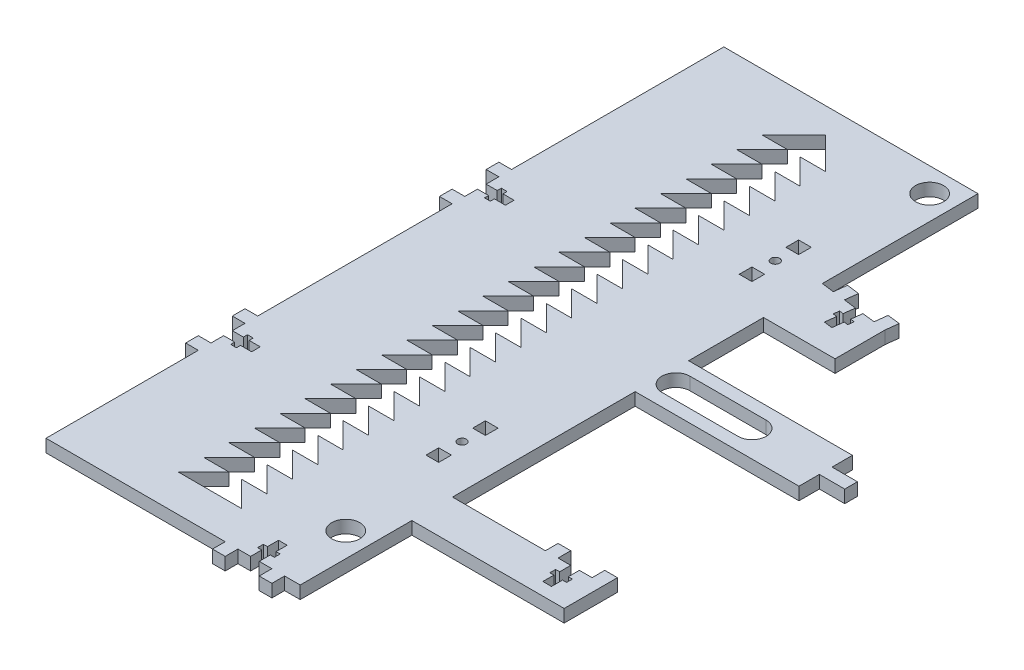
SolidWorks part; units mm, degrees
ref_plane "Front Plane" through (0, 0, 0) normal (0, 0, 1) x (1, 0, 0)
ref_plane "Top Plane" through (0, 0, 0) normal (0, 1, 0) x (1, 0, 0)
ref_plane "Right Plane" through (0, 0, 0) normal (1, 0, 0) x (0, 0, -1)
sketch "Axle Support Plate" plane through (0, 0, 0) normal (0, 1, 0) x (1, 0, 0)
  line L0 (51.4759, 157.4574) -> (51.4759, -134.6426) construction
  line L1 (38.7759, 169.5676) -> (38.7759, -103.4054) construction
  line L2 (0, 156.8676) -> (-15.875, 140.9926)
  line L3 (-15.875, 140.9926) -> (-3.175, 140.9926)
  line L4 (63.5861, -169.5676) -> (63.5861, -113.6876)
  line L5 (-63.5861, 169.5676) -> (63.5861, -169.5676) construction
  line L6 (-63.5861, -169.5676) -> (63.5861, 169.5676) construction
  line L7 (-63.5861, -63.6496) -> (-63.5861, 33.6324)
  line L8 (-63.5861, 169.5676) -> (63.5861, 169.5676)
  line L9 (0, 169.5676) -> (0, -169.5676) construction
  line L10 (15.875, 140.9926) -> (0, 156.8676)
  line L11 (-3.175, 140.9926) -> (-15.875, 128.2926)
  line L12 (-15.875, 128.2926) -> (-3.175, 128.2926)
  line L13 (15.875, 128.2926) -> (3.175, 140.9926)
  line L14 (-3.175, 128.2926) -> (-15.875, 115.5926)
  line L15 (-15.875, 115.5926) -> (-3.175, 115.5926)
  line L16 (15.875, 115.5926) -> (3.175, 128.2926)
  line L17 (63.5861, 11.4074) -> (4.2777, 11.4074) construction
  line L18 (-3.175, 115.5926) -> (-15.875, 102.8926)
  line L19 (-15.875, 102.8926) -> (-3.175, 102.8926)
  line L20 (15.875, 102.8926) -> (3.175, 115.5926)
  line L21 (-3.175, 102.8926) -> (-15.875, 90.1926)
  line L22 (-15.875, 90.1926) -> (-3.175, 90.1926)
  line L23 (55.7939, -169.5676) -> (63.5861, -169.5676)
  line L24 (15.875, 90.1926) -> (3.175, 102.8926)
  line L25 (-3.175, 90.1926) -> (-15.875, 77.4926)
  line L26 (-15.875, 77.4926) -> (-3.175, 77.4926)
  line L27 (15.875, 77.4926) -> (3.175, 90.1926)
  line L28 (-3.175, 77.4926) -> (-15.875, 64.7926)
  line L29 (-15.875, 64.7926) -> (-3.175, 64.7926)
  line L30 (15.875, 64.7926) -> (3.175, 77.4926)
  line L31 (-3.175, 64.7926) -> (-15.875, 52.0926)
  line L32 (-15.875, 52.0926) -> (-3.175, 52.0926)
  line L33 (15.875, 52.0926) -> (3.175, 64.7926)
  line L34 (-3.175, 52.0926) -> (-15.875, 39.3926)
  line L35 (-15.875, 39.3926) -> (-3.175, 39.3926)
  line L36 (15.875, 39.3926) -> (3.175, 52.0926)
  line L37 (63.5861, 24.7876) -> (145.5462, 24.7876)
  line L38 (145.5462, 24.7876) -> (145.5462, 14.5824)
  line L39 (145.5462, -1.9727) -> (63.5861, -1.9727)
  line L40 (70.6162, 11.4074) -> (108.7162, 11.4074) construction
  line L41 (70.6162, 18.4376) -> (108.7162, 18.4376)
  line L42 (70.6162, 4.3773) -> (108.7162, 4.3773)
  line L43 (145.5462, 8.2324) -> (158.2462, 8.2324)
  line L44 (158.2462, 8.2324) -> (158.2462, 14.5824)
  line L45 (158.2462, 14.5824) -> (145.5462, 14.5824)
  line L46 (63.5861, 24.7876) -> (63.5861, 169.5676)
  line L47 (63.5861, 24.7876) -> (63.5861, -1.9727) construction
  line L48 (63.5861, 11.4074) -> (158.2462, 11.4074) construction
  line L49 (-3.175, 39.3926) -> (-15.875, 26.6926)
  line L50 (-15.875, 26.6926) -> (-3.175, 26.6926)
  line L51 (145.5462, 8.2324) -> (145.5462, -1.9727)
  line L52 (15.875, 26.6926) -> (3.175, 39.3926)
  line L53 (-3.175, 26.6926) -> (-15.875, 13.9926)
  line L54 (-15.875, 13.9926) -> (-3.175, 13.9926)
  line L55 (15.875, 13.9926) -> (3.175, 26.6926)
  line L56 (-3.175, 13.9926) -> (-15.875, 1.2926)
  line L57 (-15.875, 1.2926) -> (-3.175, 1.2926)
  line L58 (15.875, 1.2926) -> (3.175, 13.9926)
  line L59 (3.175, -11.4074) -> (15.875, -11.4074)
  line L60 (-15.875, -11.4074) -> (-3.175, -11.4074)
  line L61 (15.875, -11.4074) -> (3.175, 1.2926)
  line L62 (-3.175, -11.4074) -> (-15.875, -24.1074)
  line L63 (-15.875, -24.1074) -> (-3.175, -24.1074)
  line L64 (15.875, -24.1074) -> (3.175, -11.4074)
  line L65 (-3.175, -24.1074) -> (-15.875, -36.8074)
  line L66 (-15.875, -36.8074) -> (-3.175, -36.8074)
  line L67 (15.875, -36.8074) -> (3.175, -24.1074)
  line L68 (-3.175, -36.8074) -> (-15.875, -49.5074)
  line L69 (-15.875, -49.5074) -> (-3.175, -49.5074)
  line L70 (15.875, -49.5074) -> (3.175, -36.8074)
  line L71 (-3.175, -49.5074) -> (-15.875, -62.2074)
  line L72 (-15.875, -62.2074) -> (-3.175, -62.2074)
  line L73 (15.875, -62.2074) -> (3.175, -49.5074)
  line L74 (-3.175, -62.2074) -> (-15.875, -74.9074)
  line L75 (-15.875, -74.9074) -> (-3.175, -74.9074)
  line L76 (15.875, -74.9074) -> (3.175, -62.2074)
  line L77 (-3.175, -74.9074) -> (-15.875, -87.6074)
  line L78 (-15.875, -87.6074) -> (-3.175, -87.6074)
  line L79 (15.875, -87.6074) -> (3.175, -74.9074)
  line L80 (-3.175, -87.6074) -> (-15.875, -100.3074)
  line L81 (-63.5861, 63.3504) -> (-63.5861, 169.5676)
  line L82 (-15.875, -100.3074) -> (-3.175, -100.3074)
  line L83 (15.875, -100.3074) -> (3.175, -87.6074)
  line L84 (-3.175, -100.3074) -> (-15.875, -113.0074)
  line L85 (-15.875, -113.0074) -> (-3.175, -113.0074)
  line L86 (15.875, -113.0074) -> (3.175, -100.3074)
  line L87 (-3.175, -113.0074) -> (-15.875, -125.7074)
  line L88 (-15.875, -125.7074) -> (-3.175, -125.7074)
  line L89 (15.875, -125.7074) -> (3.175, -113.0074)
  line L90 (26.0759, -169.5676) -> (-63.5861, -169.5676)
  line L91 (-3.175, -125.7074) -> (-15.875, -138.4074)
  line L92 (-15.875, -138.4074) -> (-3.175, -138.4074)
  line L93 (15.875, -138.4074) -> (3.175, -125.7074)
  line L94 (-63.5861, -169.5676) -> (-63.5861, -93.3676)
  line L95 (-3.175, -138.4074) -> (-15.875, -151.1074)
  line L96 (-15.875, -151.1074) -> (15.875, -151.1074)
  line L97 (15.875, -151.1074) -> (3.175, -138.4074)
  line L98 (3.175, 140.9926) -> (15.875, 140.9926)
  line L99 (3.175, 115.5926) -> (15.875, 115.5926)
  line L100 (3.175, 128.2926) -> (15.875, 128.2926)
  line L101 (3.175, 102.8926) -> (15.875, 102.8926)
  line L102 (3.175, 77.4926) -> (15.875, 77.4926)
  line L103 (3.175, 90.1926) -> (15.875, 90.1926)
  line L104 (3.175, 64.7926) -> (15.875, 64.7926)
  line L105 (3.175, 52.0926) -> (15.875, 52.0926)
  line L106 (3.175, 39.3926) -> (15.875, 39.3926)
  line L107 (3.175, 26.6926) -> (15.875, 26.6926)
  line L108 (3.175, 13.9926) -> (15.875, 13.9926)
  line L109 (3.175, 1.2926) -> (15.875, 1.2926)
  line L110 (-3.175, 1.2926) -> (-15.875, -11.4074)
  line L111 (0, 4.4676) -> (-1.2184, 3.2492) [skipped]
  line L112 (3.175, -24.1074) -> (15.875, -24.1074)
  line L113 (3.175, -36.8074) -> (15.875, -36.8074)
  line L114 (3.175, -49.5074) -> (15.875, -49.5074)
  line L115 (3.175, -62.2074) -> (15.875, -62.2074)
  line L116 (3.175, -74.9074) -> (15.875, -74.9074)
  line L117 (3.175, -87.6074) -> (15.875, -87.6074)
  line L118 (3.175, -100.3074) -> (15.875, -100.3074)
  line L119 (3.175, -113.0074) -> (15.875, -113.0074)
  line L120 (3.175, -125.7074) -> (15.875, -125.7074)
  line L121 (3.175, -138.4074) -> (15.875, -138.4074)
  line L122 (139.7861, -93.3676) -> (139.7861, -113.6876)
  line L123 (139.7861, -113.6876) -> (63.5861, -113.6876)
  line L124 (110.0681, -93.3676) -> (63.5861, -93.3676)
  line L125 (63.5861, -93.3676) -> (63.5861, -1.9727)
  circle A0 centre (51.4759, 157.4574) radius 7.0301
  circle A1 centre (51.4759, -134.6426) radius 7.0301
  arc A4 (70.6162, 18.4376) -> (70.6162, 4.3773) centre (70.6162, 11.4074) ccw
  arc A5 (108.7162, 4.3773) -> (108.7162, 18.4376) centre (108.7162, 11.4074) ccw
  point P8 (0, 0)
  point P15 (51.4759, 11.4074)
  point P57 (89.6662, 11.4074)
  line B0 (-63.5861, -69.9996) -> (-69.9361, -69.9996)
  line B1 (-69.9361, -69.9996) -> (-69.9361, -63.6496)
  line B2 (-69.9361, -63.6496) -> (-63.5861, -63.6496)
  line B3 (-63.5861, -76.3496) -> (-58.0511, -76.3496)
  line B4 (-58.0511, -76.3496) -> (-58.0511, -74.3086)
  line B5 (-58.0511, -74.3086) -> (-55.1511, -74.3086)
  line B6 (-55.1511, -74.3086) -> (-55.1511, -76.3496)
  line B7 (-55.1511, -76.3496) -> (-49.6161, -76.3496)
  line B8 (-49.6161, -76.3496) -> (-49.6161, -80.6676)
  line B9 (-49.6161, -80.6676) -> (-55.1511, -80.6676)
  line B10 (-55.1511, -80.6676) -> (-55.1511, -82.7086)
  line B11 (-55.1511, -82.7086) -> (-58.0511, -82.7086)
  line B12 (-58.0511, -82.7086) -> (-58.0511, -80.6676)
  line B13 (-58.0511, -80.6676) -> (-63.5861, -80.6676)
  line B14 (-49.6161, -78.5086) -> (-63.5861, -78.5086) construction
  line B15 (-63.5861, -87.0176) -> (-63.5861, -80.6676)
  line B16 (-69.9361, -93.3676) -> (-63.5861, -93.3676)
  line B17 (-63.5861, -69.9996) -> (-63.5861, -76.3496)
  line B18 (-69.9361, -87.0176) -> (-69.9361, -93.3676)
  line B19 (-63.5861, -87.0176) -> (-69.9361, -87.0176)
  line B20 (-63.5861, 57.0004) -> (-69.9361, 57.0004)
  line B21 (-69.9361, 57.0004) -> (-69.9361, 63.3504)
  line B22 (-69.9361, 63.3504) -> (-63.5861, 63.3504)
  line B23 (-63.5861, 50.6504) -> (-58.0511, 50.6504)
  line B24 (-58.0511, 50.6504) -> (-58.0511, 52.6914)
  line B25 (-58.0511, 52.6914) -> (-55.1511, 52.6914)
  line B26 (-55.1511, 52.6914) -> (-55.1511, 50.6504)
  line B27 (-55.1511, 50.6504) -> (-49.6161, 50.6504)
  line B28 (-49.6161, 50.6504) -> (-49.6161, 46.3324)
  line B29 (-49.6161, 46.3324) -> (-55.1511, 46.3324)
  line B30 (-55.1511, 46.3324) -> (-55.1511, 44.2914)
  line B31 (-55.1511, 44.2914) -> (-58.0511, 44.2914)
  line B32 (-58.0511, 44.2914) -> (-58.0511, 46.3324)
  line B33 (-58.0511, 46.3324) -> (-63.5861, 46.3324)
  line B34 (-49.6161, 48.4914) -> (-63.5861, 48.4914) construction
  line B35 (-63.5861, 39.9824) -> (-63.5861, 46.3324)
  line B36 (-69.9361, 33.6324) -> (-63.5861, 33.6324)
  line B37 (-63.5861, 57.0004) -> (-63.5861, 50.6504)
  line B38 (-69.9361, 39.9824) -> (-69.9361, 33.6324)
  line B39 (-63.5861, 39.9824) -> (-69.9361, 39.9824)
  line B40 (32.4259, -169.5676) -> (32.4259, -175.9176)
  line B41 (32.4259, -175.9176) -> (26.0759, -175.9176)
  line B42 (26.0759, -175.9176) -> (26.0759, -169.5676)
  line B43 (38.7759, -169.5676) -> (38.7759, -164.0326)
  line B44 (38.7759, -164.0326) -> (36.7349, -164.0326)
  line B45 (36.7349, -164.0326) -> (36.7349, -161.1326)
  line B46 (36.7349, -161.1326) -> (38.7759, -161.1326)
  line B47 (38.7759, -161.1326) -> (38.7759, -155.5976)
  line B48 (38.7759, -155.5976) -> (43.0939, -155.5976)
  line B49 (43.0939, -155.5976) -> (43.0939, -161.1326)
  line B50 (43.0939, -161.1326) -> (45.1349, -161.1326)
  line B51 (45.1349, -161.1326) -> (45.1349, -164.0326)
  line B52 (45.1349, -164.0326) -> (43.0939, -164.0326)
  line B53 (43.0939, -164.0326) -> (43.0939, -169.5676)
  line B54 (40.9349, -155.5976) -> (40.9349, -169.5676) construction
  line B55 (49.4439, -169.5676) -> (43.0939, -169.5676)
  line B56 (55.7939, -175.9176) -> (55.7939, -169.5676)
  line B57 (32.4259, -169.5676) -> (38.7759, -169.5676)
  line B58 (49.4439, -175.9176) -> (55.7939, -175.9176)
  line B59 (49.4439, -169.5676) -> (49.4439, -175.9176)
  line B60 (41.9509, 74.9074) -> (41.9509, 104.6254) construction
  line B61 (39.7919, 89.7664) -> (44.1099, 89.7664) construction
  line B62 (38.7759, 98.2754) -> (45.1259, 98.2754)
  line B63 (38.7759, 98.2754) -> (38.7759, 104.6254)
  line B64 (38.7759, 104.6254) -> (45.1259, 104.6254)
  line B65 (45.1259, 98.2754) -> (45.1259, 104.6254)
  line B66 (38.7759, 98.2754) -> (45.1259, 104.6254) construction
  line B67 (38.7759, 104.6254) -> (45.1259, 98.2754) construction
  line B68 (38.7759, 74.9074) -> (45.1259, 81.2574) construction
  line B69 (38.7759, 81.2574) -> (45.1259, 74.9074) construction
  line B70 (45.1259, 81.2574) -> (45.1259, 74.9074)
  line B71 (38.7759, 74.9074) -> (45.1259, 74.9074)
  line B72 (38.7759, 81.2574) -> (38.7759, 74.9074)
  line B73 (38.7759, 81.2574) -> (45.1259, 81.2574)
  circle B74 centre (41.9509, 89.7664) radius 2.159
  line B75 (41.9509, -52.0926) -> (41.9509, -81.8106) construction
  line B76 (39.7919, -66.9516) -> (44.1099, -66.9516) construction
  line B77 (38.7759, -75.4606) -> (45.1259, -75.4606)
  line B78 (38.7759, -75.4606) -> (38.7759, -81.8106)
  line B79 (38.7759, -81.8106) -> (45.1259, -81.8106)
  line B80 (45.1259, -75.4606) -> (45.1259, -81.8106)
  line B81 (38.7759, -75.4606) -> (45.1259, -81.8106) construction
  line B82 (38.7759, -81.8106) -> (45.1259, -75.4606) construction
  line B83 (38.7759, -52.0926) -> (45.1259, -58.4426) construction
  line B84 (38.7759, -58.4426) -> (45.1259, -52.0926) construction
  line B85 (45.1259, -58.4426) -> (45.1259, -52.0926)
  line B86 (38.7759, -52.0926) -> (45.1259, -52.0926)
  line B87 (38.7759, -58.4426) -> (38.7759, -52.0926)
  line B88 (38.7759, -58.4426) -> (45.1259, -58.4426)
  circle B89 centre (41.9509, -66.9516) radius 2.159
  line B90 (133.4361, -93.3676) -> (133.4361, -87.0176)
  line B91 (133.4361, -87.0176) -> (139.7861, -87.0176)
  line B92 (139.7861, -87.0176) -> (139.7861, -93.3676)
  line B93 (127.0861, -93.3676) -> (127.0861, -98.9026)
  line B94 (127.0861, -98.9026) -> (129.1271, -98.9026)
  line B95 (129.1271, -98.9026) -> (129.1271, -101.8026)
  line B96 (129.1271, -101.8026) -> (127.0861, -101.8026)
  line B97 (127.0861, -101.8026) -> (127.0861, -107.3376)
  line B98 (127.0861, -107.3376) -> (122.7681, -107.3376)
  line B99 (122.7681, -107.3376) -> (122.7681, -101.8026)
  line B100 (122.7681, -101.8026) -> (120.7271, -101.8026)
  line B101 (120.7271, -101.8026) -> (120.7271, -98.9026)
  line B102 (120.7271, -98.9026) -> (122.7681, -98.9026)
  line B103 (122.7681, -98.9026) -> (122.7681, -93.3676)
  line B104 (124.9271, -107.3376) -> (124.9271, -93.3676) construction
  line B105 (116.4181, -93.3676) -> (122.7681, -93.3676)
  line B106 (110.0681, -87.0176) -> (110.0681, -93.3676)
  line B107 (133.4361, -93.3676) -> (127.0861, -93.3676)
  line B108 (116.4181, -87.0176) -> (110.0681, -87.0176)
  line B109 (116.4181, -93.3676) -> (116.4181, -87.0176)
  dimension "D1" = 5.08
  dimension "D4" = 14.0603
  dimension "D5" = 5.08
  dimension "D8" = 31.75
  dimension "D14" = 14.0603
  dimension "D15" = 76.2
  dimension "D16" = 6.35
  dimension "D22" = 7.0301
  dimension "D25" = 36.83
  dimension "D2" = 292.1
  dimension "D6" = 12.7
  dimension "D7" = 63.5
  dimension "D9" = 89.662
  dimension "D10" = 12.7
  dimension "D11" = 24
  dimension "D12" = 10.541
  dimension "D13" = 34.925
  dimension "D17" = 76.2
  dimension "D23" = 6.35
  dimension "D24" = 38.1
  dimension "D26" = 12.7
  dimension "D27" = 6.35
  dimension "D29" = 76.2
  dimension "D30" = 203.2
sketch_block_instance "Male T-slot assembly-1"
sketch_block "Male T-slot assembly" parameters "D1"=6.35, "D2"=6.35, "D3"=4.318, "D4"=2.9, "D5"=8.4, "D6"=13.97, "D7"=6.35
sketch_block_instance "Male T-slot assembly-2"
sketch_block_instance "Male T-slot assembly-4"
sketch_block_instance "Female T-Slot Assembly-1"
sketch_block "Female T-Slot Assembly" parameters "D4"=4.318, "D1"=6.35, "D2"=6.35, "D3"=6.35
sketch_block_instance "Female T-Slot Assembly-3"
sketch_block_instance "Male T-slot assembly-6"
extrude "Boss-Extrude1" add sketch "Axle Support Plate" along normal blind 6.35 contours L23 L4 L39 L51 L43 L44 L45 L38 L37 L46 L8 region at (59.69, 0, 165.4272)
sketch "Sketch1" plane through (0, 6.35, 0) normal (0, 1, 0) x (1, 0, 0)
  line L0 (63.5861, 24.7876) -> (63.5861, 169.5676) construction
  line L1 (99.3852, 87.2747) -> (99.3852, 62.2566)
  line L2 (99.3852, 62.2566) -> (63.5861, 62.2566)
  line L3 (44.4458, 157.4574) -> (58.5061, 157.4574) construction
  line L4 (51.4759, 164.4876) -> (51.4759, 150.4273) construction
  line L5 (69.8887, 90.8964) -> (63.5861, 91.6703)
  line L6 (63.5861, 91.6703) -> (63.5861, 62.2566)
  line L8 (63.5861, 91.6703) -> (64.3599, 97.973) construction
  line L9 (-63.5861, 66.9064) -> (63.5861, 66.9064) construction
  line L10 (-63.5861, 63.3504) -> (-63.5861, 169.5676) construction
  line L11 (55.7939, -169.5676) -> (63.5861, -169.5676) construction
  line L12 (99.3852, 87.2747) -> (265.2714, 66.9064) construction
  line L13 (63.5861, 66.9064) -> (265.2714, 66.9064) construction
  circle A0 centre (51.4759, 157.4574) radius 7.0301 construction
  point P12 (51.4759, 157.4574)
  point P21 (59.69, -169.5676)
  line B0 (93.0826, 88.0486) -> (93.8564, 94.3512)
  line B1 (93.8564, 94.3512) -> (100.1591, 93.5774)
  line B2 (100.1591, 93.5774) -> (99.3852, 87.2747)
  line B3 (86.7799, 88.8224) -> (86.1053, 83.3287)
  line B4 (86.1053, 83.3287) -> (88.1311, 83.08)
  line B5 (88.1311, 83.08) -> (87.7777, 80.2016)
  line B6 (87.7777, 80.2016) -> (85.7519, 80.4503)
  line B7 (85.7519, 80.4503) -> (85.0774, 74.9566)
  line B8 (85.0774, 74.9566) -> (80.7916, 75.4828)
  line B9 (80.7916, 75.4828) -> (81.4661, 80.9765)
  line B10 (81.4661, 80.9765) -> (79.4403, 81.2253)
  line B11 (79.4403, 81.2253) -> (79.7937, 84.1037)
  line B12 (79.7937, 84.1037) -> (81.8195, 83.8549)
  line B13 (81.8195, 83.8549) -> (82.4941, 89.3487)
  line B14 (82.9345, 75.2197) -> (84.637, 89.0856) construction
  line B15 (76.1914, 90.1225) -> (82.4941, 89.3487)
  line B16 (70.6626, 97.1991) -> (69.8887, 90.8964)
  line B17 (93.0826, 88.0486) -> (86.7799, 88.8224)
  line B18 (76.9653, 96.4252) -> (70.6626, 97.1991)
  line B19 (76.1914, 90.1225) -> (76.9653, 96.4252)
  dimension "D1" = 7
  dimension "D2" = 12.7
  dimension "D3" = 203.2
  dimension "D4" = 6.35
  dimension "D5" = 236.474
sketch_block_instance "Male T-slot assembly-9"
extrude "Boss-Extrude2" add sketch "Sketch1" against normal blind 6.35 contours B15 B19 B18 B16 L6 L2 L1 B2 B1 B0 B17 B3 B4 B5 B6 B7 B8 B9 B10 B11 B12 B13 region at (98.8794, 6.35, -74.7656)
equation "\"Ball Diameter\"= 1.75in"
equation "\"Sheet Thickness\"= 0.25in"
equation "\"Screw Diameter\"= .17in"
equation "\"Robot Diameter\"= 14in"
equation "\"Castor Screw Diameter\"= 0.22in"
equation "\"Wheel Diameter\" = 4in"
equation "\"Nut Diameter\" = 8.4mm"
equation "\"Nut Height\" = 2.9mm"
equation "\"Screw Height\" = 0.55in"
equation "\"Pulley Diameter\" = 1in"
equation "\"Reactor Height\" = 14in"
equation "\"Elevator Height\" = 11.5in"
equation "\"Elevator Width\" = \"Ball Diameter\" + 0.25in"
equation "\"D1@Boss-Extrude1\"=\"Sheet Thickness\""
equation "\"Elevator Bearing Diameter\" = sqr(2*(\"Sheet Thickness\"^2)) + 0.2in"
equation "\"Elevator Axle Length\" = \"Elevator Width\" + 8*\"Sheet Thickness\""
equation "\"D4@Axle Support Plate\"=\"Elevator Bearing Diameter\""
equation "\"D6@Axle Support Plate\"=(\"Pulley Diameter\")/2"
equation "\"D13@Axle Support Plate\"=2.5in - \"Sheet Thickness\" - (\"Ball Diameter\")/2"
equation "\"D9@Axle Support Plate\"=\"Elevator Clearance from Axis\" + \"Sheet Thickness\""
equation "\"D14@Axle Support Plate\" = \"Elevator Bearing Diameter\""
equation "\"D22@Axle Support Plate\"=\"Elevator Bearing Diameter\"/2"
equation "\"D23@Axle Support Plate\" = \"Sheet Thickness\""
equation "\"Elevator Axle Endcap Diameter\" = \"Pulley Diameter\" + 0.25in"
equation "\"D25@Axle Support Plate\"=\"Elevator Axle Endcap Diameter\"+0.2in"
equation "\"D27@Axle Support Plate\"=\"Sheet Thickness\""
equation "\"Elevator Clearance from Axis\" = 3.28in"
equation "\"D3@Sketch1\"=\"Length of Chute\""
equation "\"Ball Radius\" = \"Ball Diameter\"/2"
equation "\"Elevator Horizontal Clearance\" = \"Elevator Width\" + 0.5in"
equation "\"Claw Horizontal Seperation\" = (\"Elevator Width\"/2) - (1.5 * \"Sheet Thickness\") - 0.15in"
equation "\"Claw Radius\" = \"Ball Radius\" + 0.1in"
equation "\"Castor Wheel Height\" = 1.25in"
equation "\"Length of Chute\" = 8in"
